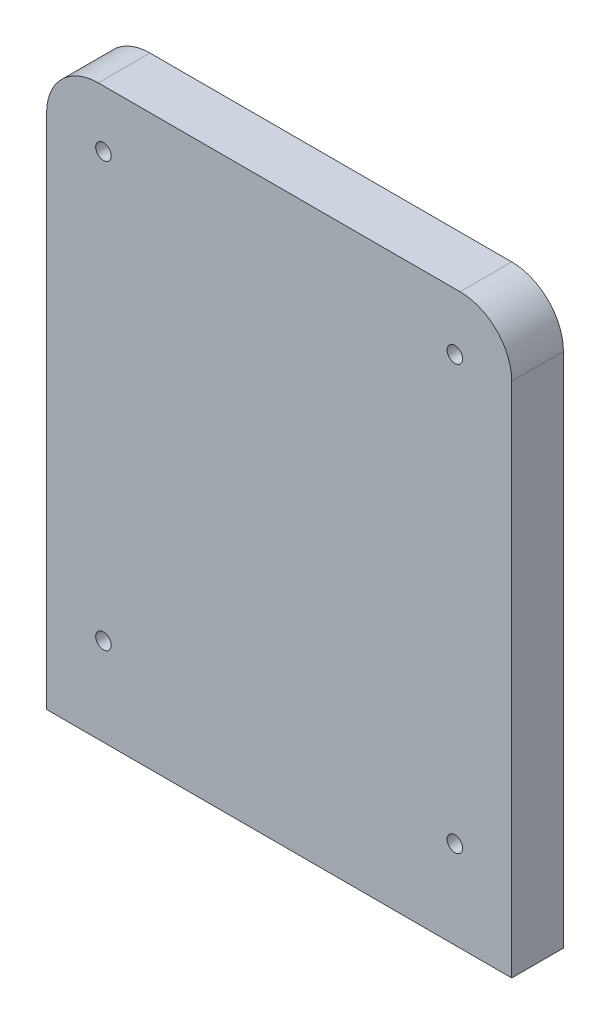
SolidWorks part; units mm, degrees
ref_plane "Спереди" through (0, 0, 0) normal (0, 0, 1) x (1, 0, 0)
ref_plane "Сверху" through (0, 0, 0) normal (0, 1, 0) x (1, 0, 0)
ref_plane "Справа" through (0, 0, 0) normal (1, 0, 0) x (0, 0, -1)
sketch "Эскиз1" plane through (0, 0, 0) normal (0, 0, 1) x (1, 0, 0)
  line L1 (45, -55) -> (-45, -55)
  line L2 (45, -55) -> (45, 45)
  line L3 (35, 55) -> (-35, 55)
  line L4 (-45, -55) -> (-45, 45)
  line L5 (45, -55) -> (-45, 55) construction
  line L6 (45, 55) -> (-45, -55) construction
  arc A0 (45, 45) -> (35, 55) centre (35, 45) ccw
  arc A1 (-35, 55) -> (-45, 45) centre (-35, 45) ccw
  point P0 (0, 0)
  dimension "D3" = 10
  dimension "D1" = 90
  dimension "D2" = 110
extrude "Бобышка-Вытянуть2" add sketch "Эскиз1" along normal mid plane 10
sketch "Эскиз2" plane through (0, 0, 5) normal (0, 0, 1) x (1, 0, 0)
  line L5 (35, 55) -> (-35, 55) construction
  line L6 (40, -44) -> (-40, -44) construction
  line L7 (40, -44) -> (40, 50) construction
  line L8 (40, 50) -> (-40, 50) construction
  line L9 (-40, -44) -> (-40, 50) construction
  line L10 (40, -44) -> (-40, 50) construction
  line L11 (40, 50) -> (-40, -44) construction
  line L12 (45, -55) -> (45, 45) construction
  point P0 (0, 3)
  dimension "D1" = 5
  dimension "D2" = 80
  dimension "D3" = 5
  dimension "D4" = 94
sketch "Эскиз3" plane through (0, 0, 5) normal (0, 0, 1) x (1, 0, 0)
  line L1 (40, 50) -> (-40, 50) construction
  line L3 (-40, -44) -> (-40, 50) construction
  line L4 (0, 0) -> (0, 22.2229) construction
  line L6 (0, 3) -> (-8.2285, 3) construction
  circle A0 centre (-34, 44) radius 1.5
  circle A1 centre (34, 44) radius 1.5
  circle A2 centre (34, -38) radius 1.5
  circle A3 centre (-34, -38) radius 1.5
  dimension "D1" = 6
  dimension "D2" = 6
extrude "Вырез-Вытянуть1" cut sketch "Эскиз3" against normal up to surface (10 mm away) up to face at (0, 15.6904, -5)
